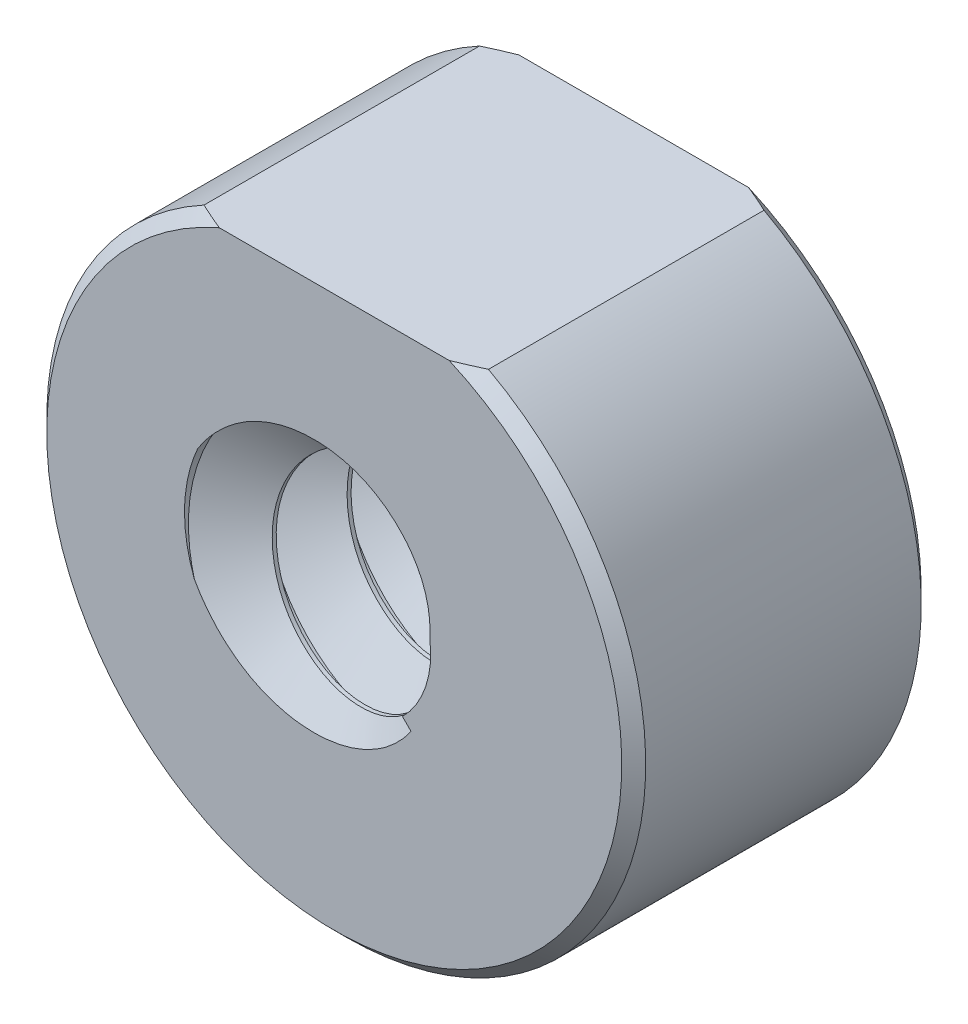
SolidWorks part; units mm, degrees
ref_plane "Front Plane" through (0, 0, 0) normal (0, 0, 1) x (1, 0, 0)
ref_plane "Top Plane" through (0, 0, 0) normal (0, 1, 0) x (1, 0, 0)
ref_plane "Right Plane" through (0, 0, 0) normal (1, 0, 0) x (0, 0, -1)
sketch "Sketch1" plane through (0, 0, 0) normal (0, 0, 1) x (1, 0, 0)
  line L0 (0, 0) -> (0, 5.588) construction
  line L1 (-3.0161, 5.588) -> (3.0161, 5.588)
  arc A0 (-3.0161, 5.588) -> (3.0161, 5.588) centre (0, 0) ccw
  circle A1 centre (0, 0) radius 2.0447
  point P8 (0, 5.588)
  dimension "D1" = 12.7
  dimension "D2" = 4.0894
  dimension "D3" = 5.588
extrude "Boss-Extrude1" add sketch "Sketch1" along normal blind 6.35
sketch "Sketch2" plane through (0, 0, 0) normal (1, 0, 0) x (0, 0, -1)
  line L0 (1.1412, 0) -> (-8.5448, 0) construction
  line L1 (1.1412, 2.0447) -> (0.4886, 3.175)
  line L2 (0.4886, 3.175) -> (0.2902, 3.175)
  line L3 (0.2902, 3.175) -> (-0.3624, 2.0447)
  line L4 (-0.3624, 2.0447) -> (1.1412, 2.0447)
  dimension "D1" = 4.0894
  dimension "D2" = 6.35
  dimension "D3" = 60
  dimension "D4" = 60
  dimension "D5" = 0.1984
sketch "Sketch3" plane through (0, 0, 0) normal (0, 0, -1) x (-1, 0, 0)
  circle A0 centre (0, 0) radius 2.728
  dimension "D1" = 5.4559
curve "Helix/Spiral1" pitch 1.5875 height 7.5406 turns 4.75
sweep "Cut-Sweep1" cut profiles "Sketch2" path "Helix/Spiral1"
chamfer "Chamfer1" distance 0.254 angle 45 2 edges at (0, -6.35, 6.35) (0, -6.35, 0)
